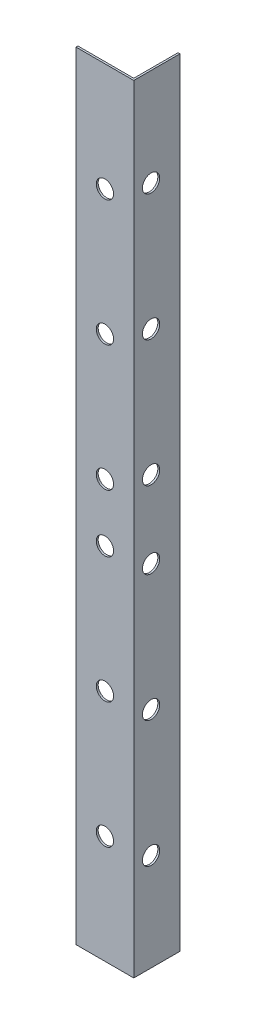
SolidWorks part; units mm, degrees
material "6061-T6 (SS)"
ref_plane "Alzado" through (0, 0, 0) normal (0, 0, 1) x (1, 0, 0)
ref_plane "Planta" through (0, 0, 0) normal (0, 1, 0) x (1, 0, 0)
ref_plane "Vista lateral" through (0, 0, 0) normal (1, 0, 0) x (0, 0, -1)
sketch "Sketch1" plane through (0, 0, 0) normal (0, 1, 0) x (1, 0, 0)
  line L0 (0, 0) -> (15, 0)
  line L1 (15, 0) -> (15, 12)
  line L2 (15, 12) -> (14.5, 12)
  line L3 (14.5, 12) -> (14.5, 0.5)
  line L4 (14.5, 0.5) -> (0, 0.5)
  line L5 (0, 0.5) -> (0, 0)
  dimension "D1" = 15
  dimension "D2" = 12
  dimension "D3" = 0.5
  dimension "D4" = 0.5
extrude "Boss-Extrude1" add sketch "Sketch1" along normal blind 202
sketch "Sketch2" plane through (0, 0, 0) normal (0, 0, 1) x (1, 0, 0)
  circle A0 centre (7.5, 173.8333) radius 2.25
  circle A1 centre (7.5, 141.1667) radius 2.25
  circle A2 centre (7.5, 108.5) radius 2.25
  circle A3 centre (7.5, 93.5) radius 2.25
  circle A4 centre (7.5, 60.8333) radius 2.25
  circle A5 centre (7.5, 28.1667) radius 2.25
  dimension "D1" = 4.5
extrude "Cut-Extrude1" cut sketch "Sketch2" against normal up to next
sketch "Sketch3" plane through (15, 0, 0) normal (1, 0, 0) x (0, 0, -1)
  circle A0 centre (4.5, 25.3333) radius 2.25
  circle A1 centre (4.5, 58.1667) radius 2.25
  circle A2 centre (4.5, 91) radius 2.25
  circle A3 centre (4.5, 111) radius 2.25
  circle A4 centre (4.5, 143.8333) radius 2.25
  circle A5 centre (4.5, 176.6667) radius 2.25
  dimension "D1" = 4.5
extrude "Cut-Extrude2" cut sketch "Sketch3" against normal up to next
